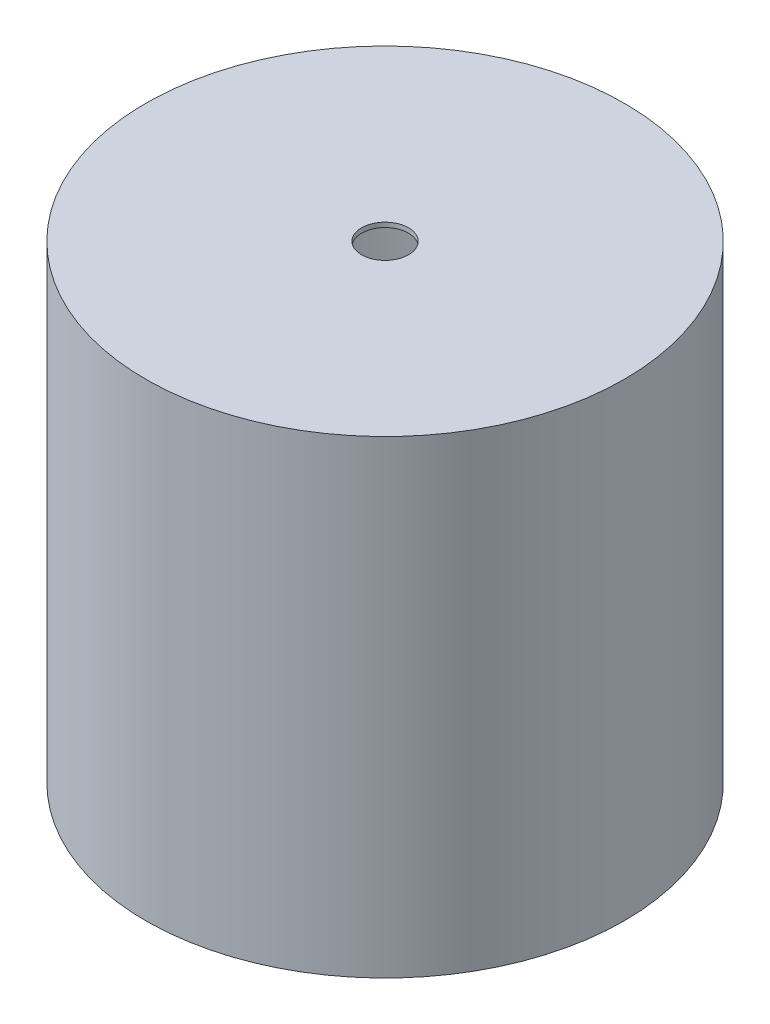
SolidWorks part; units mm, degrees
ref_plane "Front" through (0, 0, 0) normal (0, 0, 1) x (1, 0, 0)
ref_plane "Top" through (0, 0, 0) normal (0, 1, 0) x (1, 0, 0)
ref_plane "Right" through (0, 0, 0) normal (1, 0, 0) x (0, 0, -1)
sketch "Sketch1" plane through (0, 0, 0) normal (0, 1, 0) x (1, 0, 0)
  circle A0 centre (0, 0) radius 50
  dimension "D1" = 100
extrude "Extrude-Thin1" add sketch "Sketch1" along normal blind 100 thin thin type one direction wall 1
extrude "Boss-Extrude1" add sketch "Sketch1<2>" along normal blind 1
sketch "Sketch1<2>" plane through (0, 0, 0) normal (0, 1, 0) x (1, 0, 0) same geometry as "Sketch1"
pattern_linear "LPattern1" count 2 spacing 99 along (0, 1, 0) of "Boss-Extrude1"
sketch "Sketch3" plane through (0, 0, 0) normal (0, -1, 0) x (1, 0, 0)
  circle A0 centre (0, 0) radius 5
  dimension "D1" = 10
extrude "Cut-Extrude1" cut sketch "Sketch3" against normal through all
extrude "Extrude-Thin2" add sketch "Sketch3<2>" against normal blind 10 thin thin type one direction wall 1
sketch "Sketch3<2>" plane through (0, 0, 0) normal (0, -1, 0) x (1, 0, 0) same geometry as "Sketch3"
sketch "Sketch5" plane through (0, 0, 0) normal (0, 0, 1) x (1, 0, 0)
  circle A0 centre (0, 5) radius 2.5
  dimension "D1" = 5
  dimension "D2" = 5
extrude "Cut-Extrude2" cut sketch "Sketch5" against normal blind 20 and the other way blind 20
